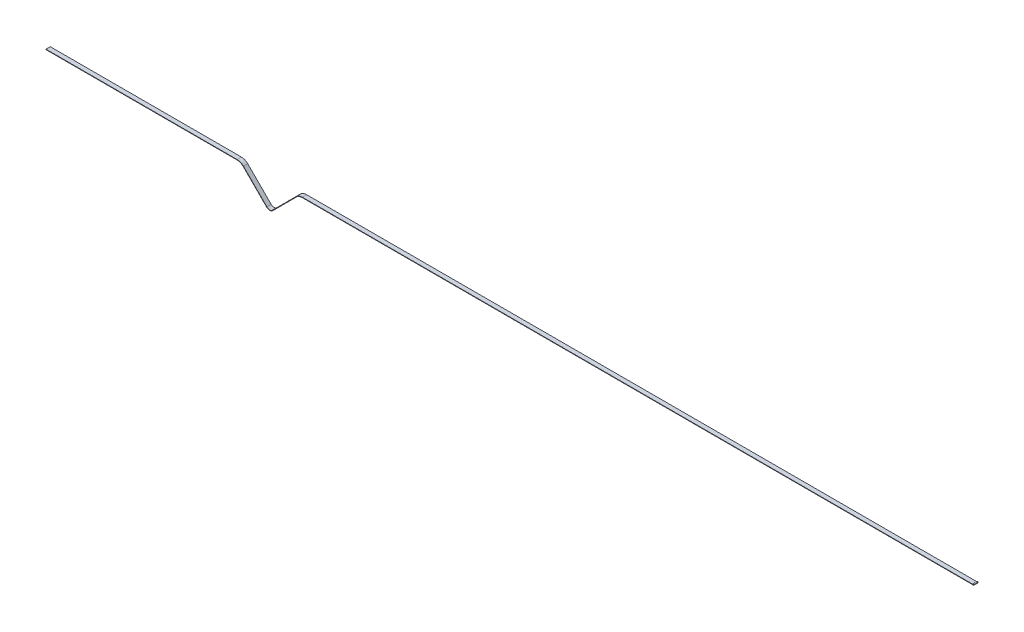
SolidWorks part; units mm, degrees
ref_plane "Front Plane" through (0, 0, 0) normal (0, 0, 1) x (1, 0, 0)
ref_plane "Top Plane" through (0, 0, 0) normal (0, 1, 0) x (1, 0, 0)
ref_plane "Right Plane" through (0, 0, 0) normal (1, 0, 0) x (0, 0, -1)
sketch "Sketch1" plane through (0, 0, 0) normal (1, 0, 0) x (0, 0, -1)
  line L1 (0, 0) -> (6, 0)
  line L2 (0, 0) -> (0, 0.63)
  line L3 (0, 0.63) -> (6, 0.63)
  line L4 (6, 0) -> (6, 0.63)
  dimension "D1" = 0.63
  dimension "D2" = 6
sketch "Sketch2" plane through (0, 0, 0) normal (0, 0, 1) x (1, 0, 0)
  line L0 (0, 0) -> (-937.7651, 0)
  line L1 (-946.2202, -3.5053) -> (-979.012, -36.3377)
  line L2 (-987.6582, -36.3377) -> (-1020.4499, -3.5053)
  line L3 (-1028.9051, 0) -> (-1295.84, 0)
  arc A0 (-937.7651, 0) -> (-946.2202, -3.5053) centre (-937.7651, -11.95) ccw
  arc A1 (-979.012, -36.3377) -> (-987.6582, -36.3377) centre (-983.3351, -32.02) cw
  arc A2 (-1020.4499, -3.5053) -> (-1028.9051, 0) centre (-1028.9051, -11.95) ccw
  circle A4 centre (-983.3351, -32.02) radius 6.11 construction
  circle A6 centre (-937.7651, -11.95) radius 11.95 construction
  circle A7 centre (-1028.9051, -11.95) radius 11.95 construction
  dimension "D1" = 6.11
  dimension "D4" = 1295.84
sweep "Sweep1" add profiles "Sketch1" path "Sketch2"
sketch "Sketch3" plane through (0, 0, 0) normal (0, 0, 1) x (1, 0, 0)
  line L0 (0, 0.63) -> (-937.7651, 0.63) construction
  line L1 (-1.5, 0.63) -> (-1.5, 0)
  line L2 (0, 0) -> (-937.7651, 0) construction
  line L3 (-1.5, 0) -> (0, 0)
  line L4 (0, 0) -> (0, 0.63)
  arc A1 (0, 0.63) -> (-1.5, 0.63) centre (-0.75, 0.63) ccw
  dimension "D1" = 0.75
extrude "Boss-Extrude1" add sketch "Sketch3" against normal through all
pattern_curve "CrvPattern1" [suppressed] of bodies 102 driven by "Sketch2" parameters "D1"=2000, "D3"=2, "D2"=1, "D4"=10
